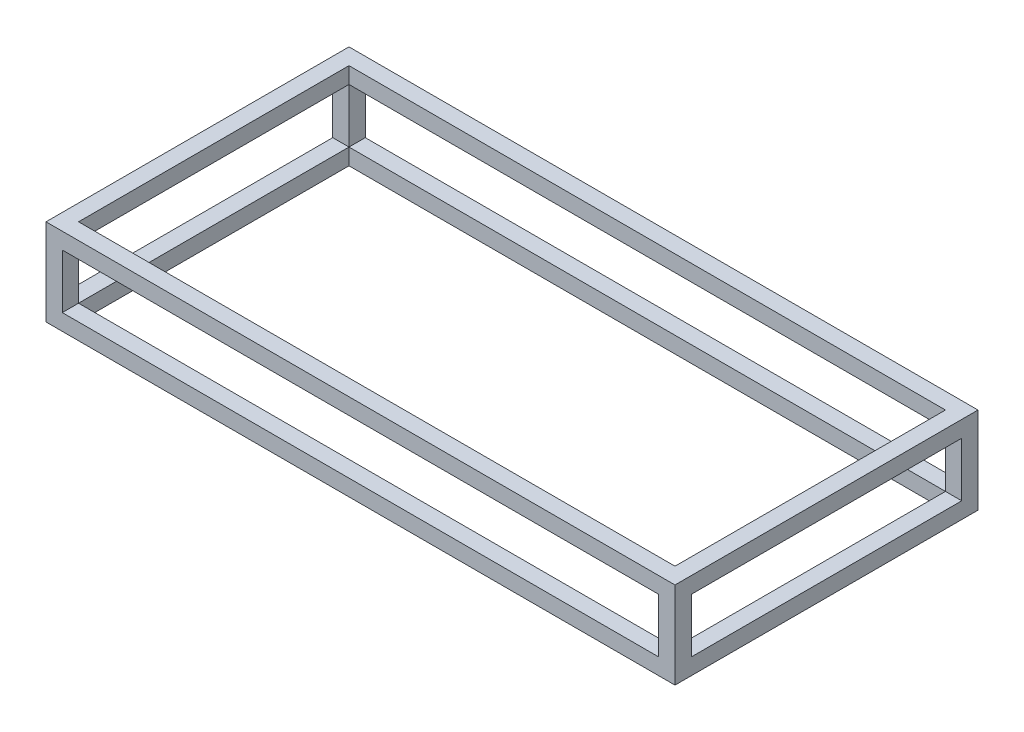
SolidWorks part; units mm, degrees
ref_plane "Front Plane" through (0, 0, 0) normal (0, 0, 1) x (1, 0, 0)
ref_plane "Top Plane" through (0, 0, 0) normal (0, 1, 0) x (1, 0, 0)
ref_plane "Right Plane" through (0, 0, 0) normal (1, 0, 0) x (0, 0, -1)
sketch "Sketch3" plane through (0, 0, 0) normal (0, 1, 0) x (1, 0, 0)
  line L1 (-275, 124.7) -> (275, 124.7)
  line L2 (-275, 124.7) -> (-275, -124.7)
  line L3 (-275, -124.7) -> (275, -124.7)
  line L4 (275, 124.7) -> (275, -124.7)
  line L5 (-275, 124.7) -> (275, -124.7) construction
  line L6 (-275, -124.7) -> (275, 124.7) construction
  line L7 (-290, 139.7) -> (290, 139.7)
  line L8 (-290, 139.7) -> (-290, -139.7)
  line L9 (-290, -139.7) -> (290, -139.7)
  line L10 (290, 139.7) -> (290, -139.7)
  line L11 (-290, 139.7) -> (290, -139.7) construction
  line L12 (-290, -139.7) -> (290, 139.7) construction
  point P0 (0, 0)
  point P6 (0, 0)
  dimension "D1" = 580
  dimension "D2" = 15
  dimension "D3" = 15
  dimension "D4" = 279.4
extrude "Boss-Extrude3" add sketch "Sketch3" along normal blind 15
sketch "Sketch4" plane through (0, 15, 0) normal (0, 1, 0) x (1, 0, 0)
  line L0 (-275, -124.7) -> (275, -124.7) construction
  line L1 (-290, 139.7) -> (-275, 139.7)
  line L2 (-290, 139.7) -> (-290, 124.7)
  line L3 (-290, 124.7) -> (-275, 124.7)
  line L4 (-275, 139.7) -> (-275, 124.7)
  line L5 (-290, -139.7) -> (-275, -139.7)
  line L6 (-290, -139.7) -> (-290, -124.7)
  line L7 (-290, -124.7) -> (-275, -124.7)
  line L8 (-275, -139.7) -> (-275, -124.7)
  line L9 (290, -139.7) -> (275, -139.7)
  line L10 (290, -139.7) -> (290, -124.7)
  line L11 (290, -124.7) -> (275, -124.7)
  line L12 (275, -139.7) -> (275, -124.7)
  line L14 (290, 139.7) -> (275, 139.7)
  line L15 (290, 139.7) -> (290, 124.7)
  line L16 (290, 124.7) -> (275, 124.7)
  line L17 (275, 139.7) -> (275, 124.7)
extrude "Boss-Extrude4" add sketch "Sketch4" along normal blind 50
sketch "Sketch5" plane through (0, 65, 0) normal (0, 1, 0) x (1, 0, 0)
  line L1 (-290, 139.7) -> (290, 139.7)
  line L2 (-290, 139.7) -> (-290, -139.7)
  line L3 (-290, -139.7) -> (290, -139.7)
  line L4 (290, 139.7) -> (290, -139.7)
  line L5 (-275, 124.7) -> (275, 124.7)
  line L6 (-275, 124.7) -> (-275, -124.7)
  line L7 (-275, -124.7) -> (275, -124.7)
  line L8 (275, 124.7) -> (275, -124.7)
extrude "Boss-Extrude6" add sketch "Sketch5" along normal blind 15
